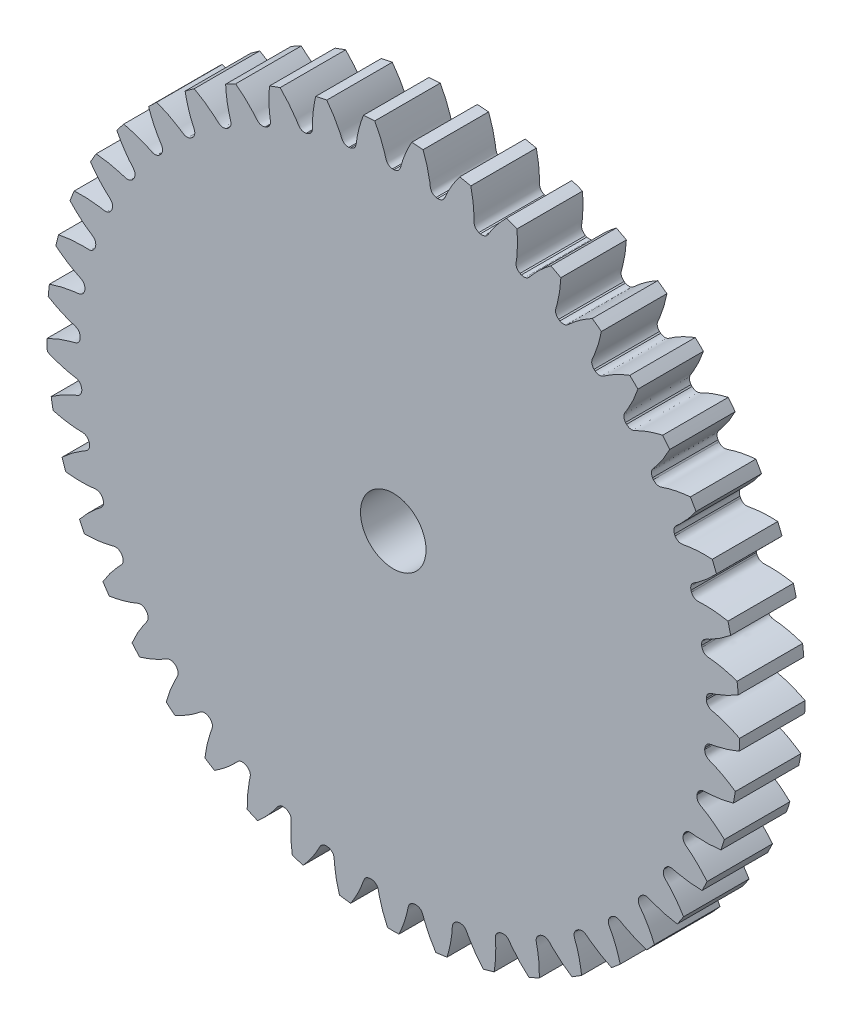
SolidWorks part; units mm, degrees
ref_plane "前视基准面" through (0, 0, 0) normal (0, 0, 1) x (1, 0, 0)
ref_plane "上视基准面" through (0, 0, 0) normal (0, 1, 0) x (1, 0, 0)
ref_plane "右视基准面" through (0, 0, 0) normal (1, 0, 0) x (0, 0, -1)
other "Configuration Table"
sketch "草图1" plane through (0, 0, 0) normal (0, 0, 1) x (1, 0, 0)
  circle A0 centre (0, 0) radius 10.575
extrude "凸台-拉伸1" add sketch "草图1" along normal blind 2
ref_axis "基准轴1" through (0, 0, 2) along (0, 0, -1)
sketch "草图2" plane through (0, 0, 0) normal (0, 0, 1) x (1, 0, 0)
  line L0 (0, 0) -> (0, 10.575) construction
  circle A0 centre (0, 0) radius 10.575 construction
  arc A1 (0.0233, 9.5625) -> (-0.0233, 9.5625) centre (0, 0) ccw
  arc A2 (1.7228, 12.0175) -> (-1.7228, 12.0175) centre (0, 0) ccw
  spline S0 degree 3 poles (0.0233, 9.5625) (0.1996, 9.5868) (0.2196, 9.7176) (0.2613, 9.8593) (0.2773, 9.9107) (0.2956, 9.9653) (0.3162, 10.0231) (0.3393, 10.084) (0.3651, 10.148) (0.3937, 10.215) (0.4251, 10.2849) (0.4596, 10.3575) (0.4972, 10.4329) (0.538, 10.5109) (0.5823, 10.5913) (0.63, 10.6742) (0.6814, 10.7593) (0.7365, 10.8467) (0.7954, 10.9361) (0.8583, 11.0274) (0.9252, 11.1205) (0.9962, 11.2154) (1.0714, 11.3118) (1.151, 11.4096) (1.2349, 11.5087) (1.3233, 11.609) (1.4163, 11.7103) (1.5483, 11.8483) (1.6517, 11.9502) (1.7228, 12.0175) knots 0 0 0 0 0.112268 0.128789 0.146568 0.165606 0.185901 0.207456 0.230268 0.254339 0.279668 0.306255 0.334101 0.363205 0.393567 0.425188 0.458067 0.492204 0.527599 0.564253 0.602166 0.641336 0.681765 0.723452 0.766398 0.810601 0.856064 0.902784 1 1 1 1
  spline S1 degree 3 poles (-0.0233, 9.5625) (-0.1996, 9.5868) (-0.2196, 9.7176) (-0.2613, 9.8593) (-0.2773, 9.9107) (-0.2956, 9.9653) (-0.3162, 10.0231) (-0.3393, 10.084) (-0.3651, 10.148) (-0.3937, 10.215) (-0.4251, 10.2849) (-0.4596, 10.3575) (-0.4972, 10.4329) (-0.538, 10.5109) (-0.5823, 10.5913) (-0.63, 10.6742) (-0.6814, 10.7593) (-0.7365, 10.8467) (-0.7954, 10.9361) (-0.8583, 11.0274) (-0.9252, 11.1205) (-0.9962, 11.2154) (-1.0714, 11.3118) (-1.151, 11.4096) (-1.2349, 11.5087) (-1.3233, 11.609) (-1.4163, 11.7103) (-1.5483, 11.8483) (-1.6517, 11.9502) (-1.7228, 12.0175) knots 0 0 0 0 0.112268 0.128789 0.146568 0.165606 0.185901 0.207456 0.230268 0.254339 0.279668 0.306255 0.334101 0.363205 0.393567 0.425188 0.458067 0.492204 0.527599 0.564253 0.602166 0.641336 0.681765 0.723452 0.766398 0.810601 0.856064 0.902784 1 1 1 1
extrude "切除-拉伸1" cut sketch "草图2" along normal through all
pattern_circular "阵列(圆周)1" count 45 every 8 about axis through (0, 0, 2) along (0, 0, -1) of "切除-拉伸1"
sketch "草图3" plane through (0, 0, 0) normal (0, 0, 1) x (1, 0, 0)
  circle A0 centre (0, 0) radius 10.125 construction
  dimension "Dn" = 20.25
sketch "草图4" plane through (0, 0, 2) normal (0, 0, 1) x (1, 0, 0)
  circle A0 centre (0, 0) radius 1
  dimension "D1" = 2
extrude "切除-拉伸2" cut sketch "草图4" against normal through all
